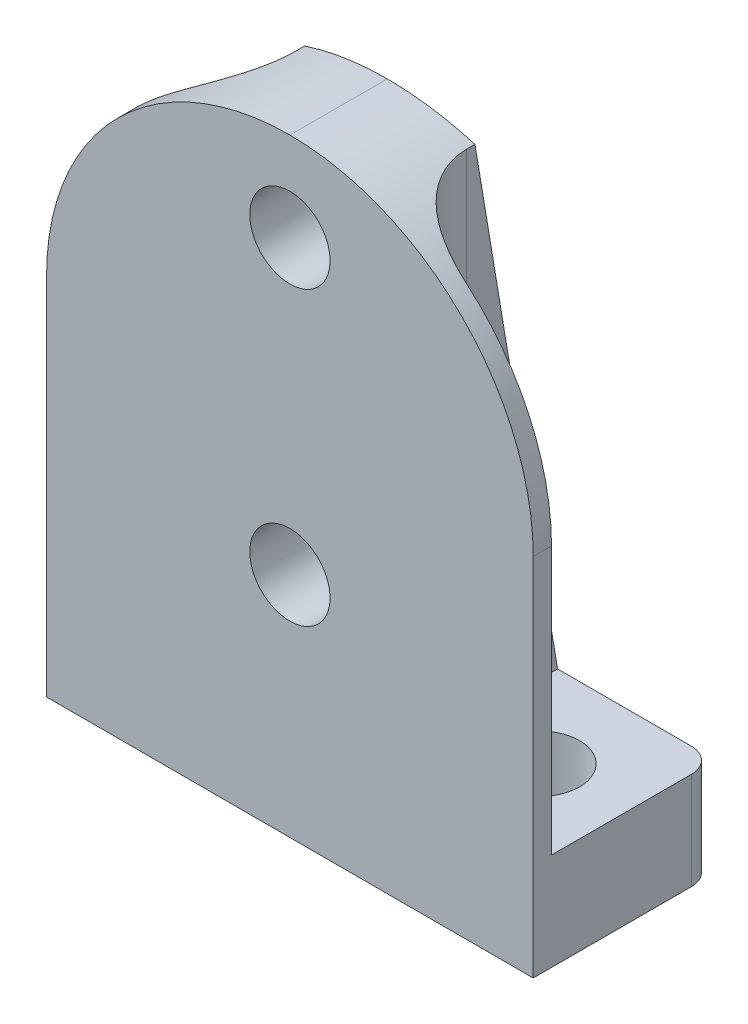
SolidWorks part; units mm, degrees
material "PETG"
ref_plane "Спереди" through (0, 0, 0) normal (0, 0, 1) x (1, 0, 0)
ref_plane "Сверху" through (0, 0, 0) normal (0, 1, 0) x (1, 0, 0)
ref_plane "Справа" through (0, 0, 0) normal (1, 0, 0) x (0, 0, -1)
sketch "Эскиз1" plane through (0, 0, 0) normal (1, 0, 0) x (0, 0, -1)
  line L0 (0, 0) -> (-9340.5259, 0) construction
  line L1 (0, 0) -> (0, 9340.5259) construction
  line L2 (0, 0) -> (7.5, 0)
  line L4 (0, 25) -> (0, 0)
  line L5 (0, 25) -> (4, 25)
  line L6 (4, 25) -> (7.5, 4)
  line L7 (7.5, 4) -> (7.5, 0)
  dimension "D1" = 7.5
  dimension "D2" = 25
  dimension "D3" = 4
extrude "Бобышка-Вытянуть1" add sketch "Эскиз1" along normal blind 20
ref_plane "Плоскость1" through (0, 0, -4) normal (0, 0, 1) x (1, 0, 0)
ref_plane "Плоскость2" through (0, 4, 0) normal (0, -1, 0) x (-1, 0, 0)
sketch "Эскиз2" plane through (0, 4, 0) normal (0, -1, 0) x (-1, 0, 0)
  line L0 (-20, 3.75) -> (0, 3.75) construction
  line L1 (-20, 0) -> (-20, 7.5) construction
  line L2 (0, 0) -> (0, 7.5) construction
  line L3 (-10, 7.5) -> (-10, 0) construction
  line L4 (-20, 7.5) -> (0, 7.5) construction
  line L5 (-20, 0) -> (0, 0) construction
  circle A0 centre (-16.5, 3.75) radius 1.65
  circle A1 centre (-3.5, 3.75) radius 1.65
  dimension "D2" = 3.3
  dimension "D1" = 13
extrude "Вырез-Вытянуть1" cut sketch "Эскиз2" along normal up to surface (4 mm away) and the other way up to surface up to face at (10, 0, -3.75) other way up to face at (10, 14.5, -5.75)
sketch "Эскиз3" plane through (0, 4, 0) normal (0, -1, 0) x (-1, 0, 0)
  circle A0 centre (-16.5, 3.75) radius 3
  circle A1 centre (-3.5, 3.75) radius 3
  dimension "D1" = 6
extrude "Вырез-Вытянуть2" cut sketch "Эскиз3" against normal up to surface (4.5 mm away) up to face at (10, 17.65, -5.225)
sketch "Эскиз4" plane through (0, 0, -4) normal (0, 0, 1) x (1, 0, 0)
  line L0 (10, 3) -> (10, 50003) construction
  line L1 (20, 4) -> (0, 4) construction
  line L4 (13.5104, 25) -> (6.4896, 25) construction
  circle A0 centre (10, 21.35) radius 1.65
  circle A1 centre (10, 9.35) radius 1.65
  point P4 (10, 4)
  dimension "D1" = 3.3
  dimension "D3" = 2
  dimension "D2" = 12
extrude "Вырез-Вытянуть3" cut sketch "Эскиз4" along normal up to surface (4 mm away) and the other way up to surface up to face at (10, 12.5, 0) other way up to face at (10, 15.625, -5.5625)
sketch "Эскиз5" plane through (0, 0, -4) normal (0, 0, 1) x (1, 0, 0)
  circle A0 centre (10, 21.35) radius 3
  circle A1 centre (10, 9.35) radius 3
  circle A2 centre (10, 21.35) radius 5 construction
  circle A3 centre (10, 9.35) radius 5 construction
  dimension "D1" = 6
  dimension "D2" = 10
extrude "Вырез-Вытянуть7" cut sketch "Эскиз5" against normal up to surface (0.6083 mm away) up to face at (10, 23, -4.3333)
sketch "Эскиз6" plane through (0, 25, 0) normal (0, 1, 0) x (1, 0, 0)
  line L0 (0, 7.5) -> (0, 0.75)
  line L1 (6.5, 3.75) -> (3.5, 3.75)
  line L2 (3.5, 0.75) -> (0, 0.75)
  line L3 (6.5, 3.75) -> (6.5, 7.5)
  line L4 (20, 7.5) -> (0, 7.5) construction
  line L5 (6.5, 7.5) -> (0, 7.5)
  line L6 (0, 4) -> (0, 0) construction
  line L7 (10, 7.5) -> (10, 0) construction
  line L8 (20, 0) -> (0, 0) construction
  line L13 (3.5, 0.75) -> (3.5, 3.75)
  line L14 (13.5, 3.75) -> (16.5, 3.75)
  line L15 (16.5, 0.75) -> (16.5, 3.75)
  line L16 (16.5, 0.75) -> (20, 0.75)
  line L17 (20, 7.5) -> (20, 0.75)
  line L18 (13.5, 7.5) -> (20, 7.5)
  line L19 (13.5, 3.75) -> (13.5, 7.5)
  arc A0 (0.5104, 4) -> (6.4896, 4) centre (3.5, 3.75) ccw construction
  circle A1 centre (3.5, 3.75) radius 3 construction
  point P5 (3.5, 0.75)
  point P20 (6.5, 3.75)
extrude "Вырез-Вытянуть8" cut sketch "Эскиз6" against normal up to surface (21 mm away) up to face at (3.5, 4, -5.4)
fillet "Скругление1" radius 10 2 edges at (0, 25, -0.375) (20, 25, -0.375)
fillet "Скругление2" radius 1 2 edges at (0, 2, -7.5) (20, 2, -7.5)
